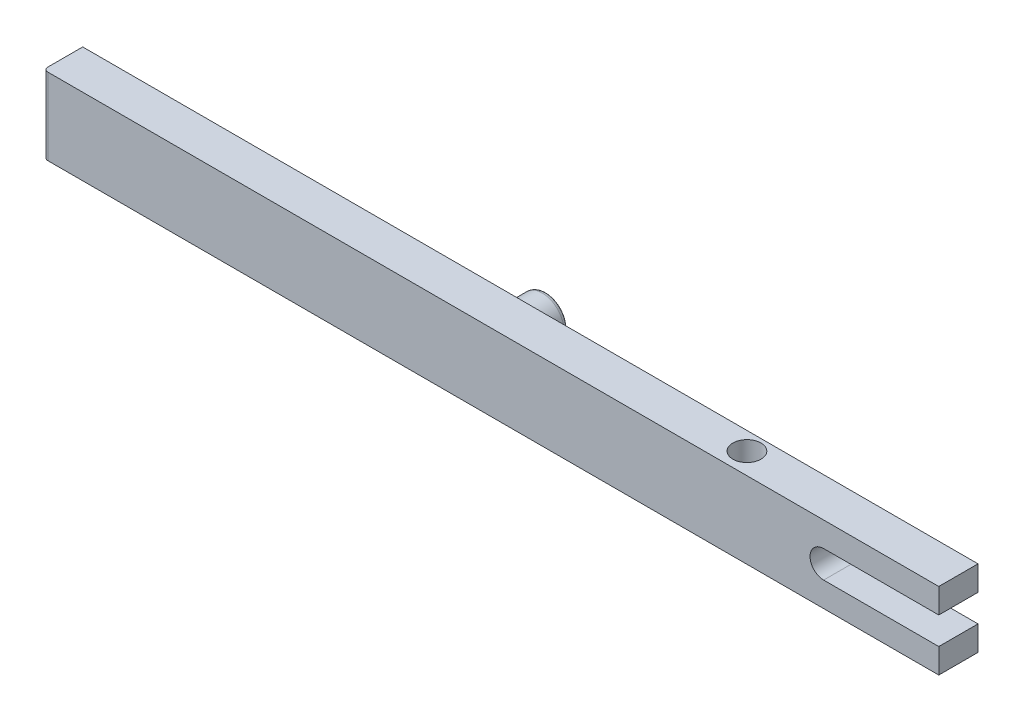
SolidWorks part; units mm, degrees
ref_plane "Front" through (0, 0, 0) normal (0, 0, 1) x (1, 0, 0)
ref_plane "Top" through (0, 0, 0) normal (0, 1, 0) x (1, 0, 0)
ref_plane "Right" through (0, 0, 0) normal (1, 0, 0) x (0, 0, -1)
sketch "Sketch1" plane through (0, 0, 0) normal (0, 0, 1) x (1, 0, 0)
  line L1 (52.5, -4.5) -> (-52.5, -4.5)
  line L2 (52.5, -4.5) -> (52.5, 4.5)
  line L3 (52.5, 4.5) -> (-52.5, 4.5)
  line L4 (-52.5, -4.5) -> (-52.5, 4.5)
  line L5 (52.5, -4.5) -> (-52.5, 4.5) construction
  line L6 (52.5, 4.5) -> (-52.5, -4.5) construction
  point P0 (0, 0)
  dimension "D1" = 9
  dimension "D2" = 105
extrude "Boss-Extrude1" add sketch "Sketch1" along normal blind 5
sketch "Sketch2" plane through (0, 4.5, 0) normal (0, 1, 0) x (1, 0, 0)
  line L0 (52.5, -5) -> (52.5, 0) construction
  line L2 (52.5, 0) -> (-52.5, 0) construction
  circle A0 centre (27.5, -2.5) radius 1.65
  dimension "D3" = 3.3
  dimension "D2" = 25
  dimension "D1" = 2.5
sketch "Sketch4" plane through (0, 0, 5) normal (0, 0, 1) x (1, 0, 0)
  line L0 (39, 0) -> (45, 0) construction
  line L1 (39, 1.6) -> (45, 1.6)
  line L2 (39, -1.6) -> (45, -1.6)
  arc A0 (39, 1.6) -> (39, -1.6) centre (39, 0) ccw
  arc A1 (45, -1.6) -> (45, 1.6) centre (45, 0) ccw
  point P2 (42, 0)
  dimension "D1" = 1.6
  dimension "D2" = 42
  dimension "D3" = 6
extrude "Cut-Extrude1" cut sketch "Sketch4" against normal blind 5
sketch "Sketch8" plane through (0, 0, 5) normal (0, 0, 1) x (1, 0, 0)
  line L0 (45, 1.6) -> (39, 1.6) construction
  line L1 (44.5, 1.6) -> (52.5, 1.6)
  line L2 (44.5, 1.6) -> (44.5, -1.6)
  line L3 (44.5, -1.6) -> (52.5, -1.6)
  line L4 (52.5, 1.6) -> (52.5, -1.6)
  line L5 (52.5, -4.5) -> (52.5, 4.5) construction
  line L6 (39, -1.6) -> (45, -1.6) construction
  dimension "D1" = 8
extrude "Cut-Extrude4" cut sketch "Sketch8" against normal blind 10
ref_plane "Plane1" through (-48.5, 0, 0) normal (-1, 0, 0) x (0, 0, 1)
chamfer "Chamfer2" distance 0.4 angle 45 8 edges at (52.5, 3.05, 0) (52.5, -3.05, 0) (0, 4.5, 0) (-52.5, 0, 0) (0, -4.5, 0) (45.75, -1.6, 0) (37.4, 0, 0) (45.75, 1.6, 0)
extrude "Cut-Extrude3" cut sketch "Sketch2" against normal blind 10
sketch "Sketch10" plane through (0, 0, 0) normal (0, 0, 1) x (1, 0, 0)
  line L2 (29.15, -4.5) -> (29.15, 4.5) construction
  circle A0 centre (-2.5, 0) radius 2.55
  dimension "D1" = 5.1
  dimension "D2" = 31.65
extrude "Boss-Extrude2" add sketch "Sketch10" against normal blind 4
fillet "Fillet1" radius 0.5 2 edges at (0.05, 0, -4) (-52.5, 0, 5)
